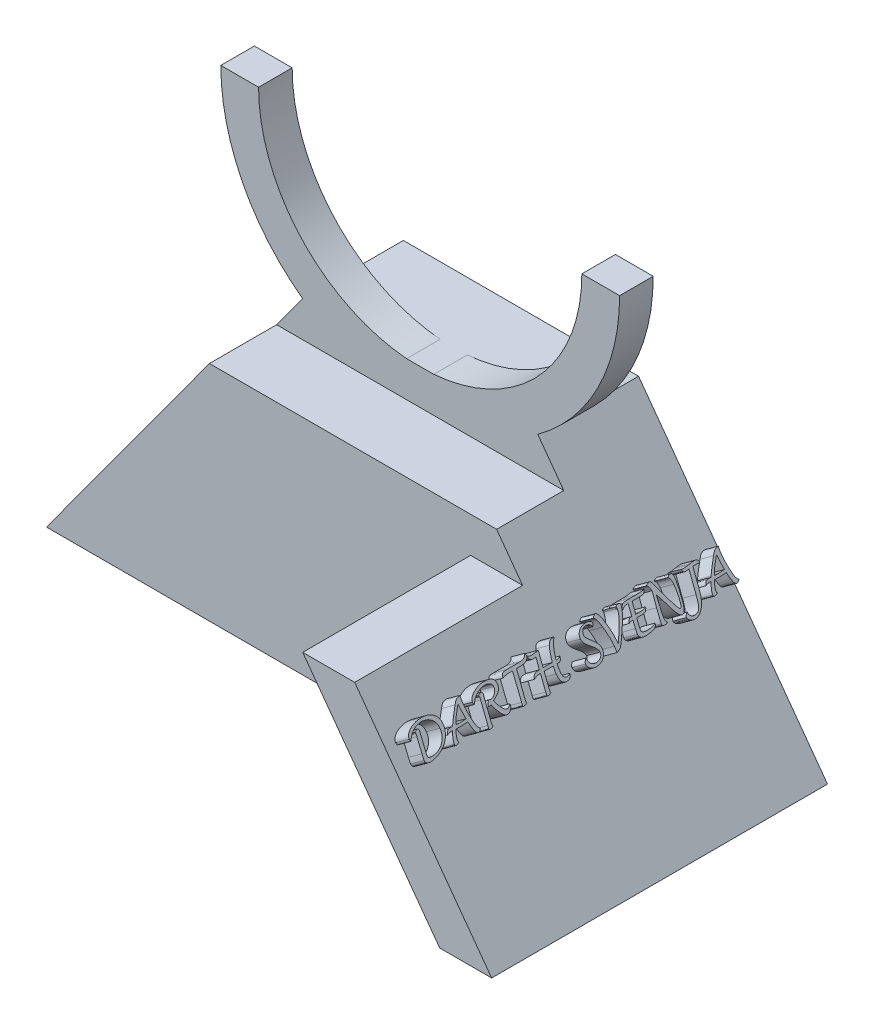
SolidWorks part; units mm, degrees
material "ABS"
ref_plane "Plan de face" through (0, 0, 0) normal (0, 0, 1) x (1, 0, 0)
ref_plane "Plan de dessus" through (0, 0, 0) normal (0, 1, 0) x (1, 0, 0)
ref_plane "Plan de droite" through (0, 0, 0) normal (1, 0, 0) x (0, 0, -1)
sketch "Esquisse1" plane through (0, 0, 0) normal (0, 0, 1) x (1, 0, 0)
  line L0 (-23.75, 0) -> (-19.25, 0)
  line L1 (19.25, 0) -> (23.75, 0)
  arc A0 (19.25, 0) -> (-19.25, 0) centre (0, 0) cw
  arc A1 (23.75, 0) -> (-23.75, 0) centre (0, 0) cw
extrude "Boss.-Extru.1" add sketch "Esquisse1" along normal blind 2 and the other way blind 2
sketch "Esquisse3" plane through (0, 0, 0) normal (0, 0, 1) x (1, 0, 0)
  line L0 (-14.0041, -19.1819) -> (14.0041, -19.1819)
  line L1 (36.51, -50) -> (-36.51, -50)
  line L2 (-36.51, -50) -> (-14.0041, -19.1819)
  line L3 (36.51, -50) -> (14.0041, -19.1819)
  arc A0 (-23.75, 0) -> (23.75, 0) centre (0, 0) ccw construction
extrude "Boss.-Extru.2" add sketch "Esquisse3" along normal blind 10 and the other way blind 10
sketch "Esquisse5" plane through (0, 0, 10) normal (0, 0, 1) x (1, 0, 0)
  line L2 (36.51, -50) -> (30.32, -50)
  line L3 (-36.51, -50) -> (36.51, -50) construction
  line L5 (14.0041, -27.6616) -> (20.1966, -27.6616)
  line L6 (14.0041, -27.6616) -> (30.32, -50)
  line L7 (20.1966, -27.6616) -> (36.51, -50)
  dimension "D1" = 6.19
extrude "Boss.-Extru.3" add sketch "Esquisse5" along normal blind 20
sketch "Esquisse6" plane through (-0.0027, -0.002, 0) normal (0.8076, 0.5898, 0) x (0, 0, -1)
  text T0 "DARTH SVENJA" font "Lucida Handwriting" height in points 12
extrude "Boss.-Extru.5" add sketch "Esquisse6" along normal blind 2
sketch "Esquisse7" plane through (0, 0, 10) normal (0, 0, 1) x (1, 0, 0)
  line L0 (-14.0041, -19.1819) -> (14.0041, -19.1819)
  line L1 (14.0041, -19.1819) -> (17.1004, -23.4218)
  line L2 (20.1966, -27.6616) -> (14.0041, -19.1819) construction
  line L3 (17.1004, -23.4218) -> (-17.1004, -23.4218)
  line L4 (-14.0041, -19.1819) -> (-36.51, -50) construction
  line L5 (-17.1004, -23.4218) -> (-14.0041, -19.1819)
extrude "Enlèv. mat.-Extru.1" cut sketch "Esquisse7" against normal up to vertex (8 mm away) up to point (1.6172, -19.1819, 2)
